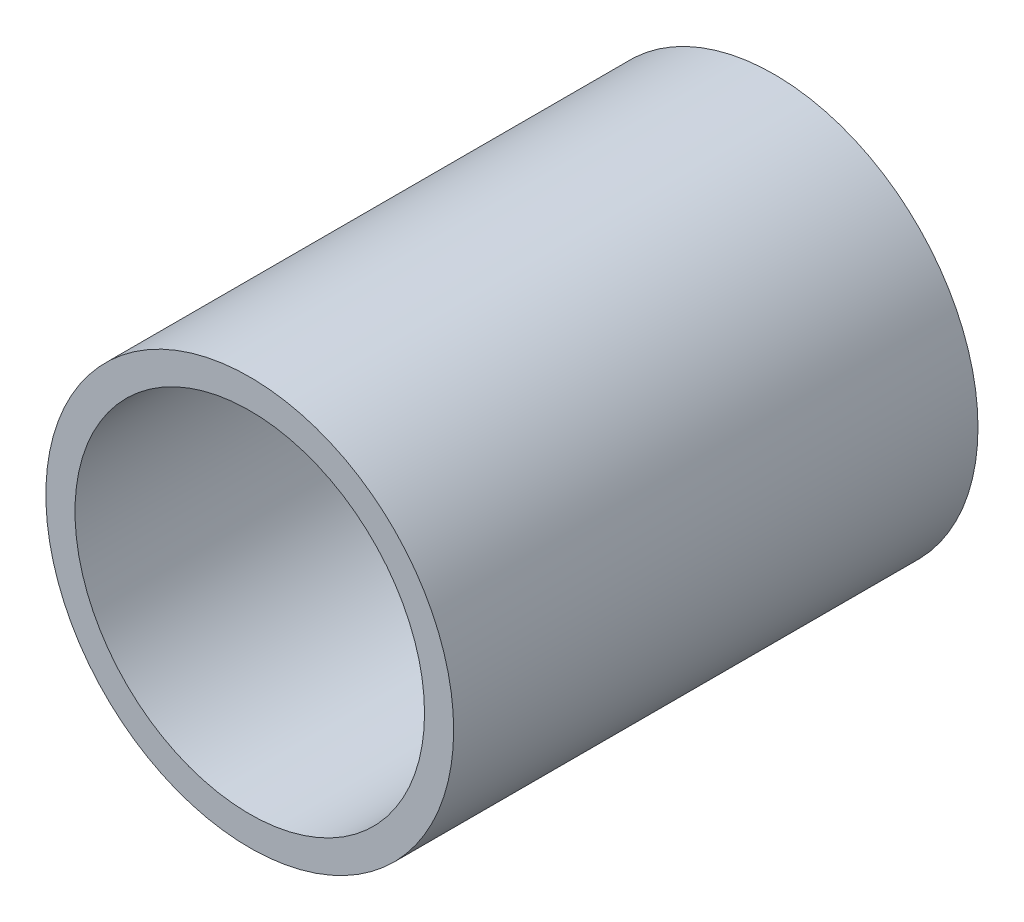
SolidWorks part; units mm, degrees
ref_plane "Front Plane" through (0, 0, 0) normal (0, 0, 1) x (1, 0, 0)
ref_plane "Top Plane" through (0, 0, 0) normal (0, 1, 0) x (1, 0, 0)
ref_plane "Right Plane" through (0, 0, 0) normal (1, 0, 0) x (0, 0, -1)
sketch "Sketch1" plane through (0, 0, 0) normal (0, 0, 1) x (1, 0, 0)
  circle A0 centre (0, 0) radius 6
  circle A1 centre (0, 0) radius 7
  dimension "D1" = 12
  dimension "D2" = 14
extrude "Boss-Extrude1" add sketch "Sketch1" along normal blind 18
